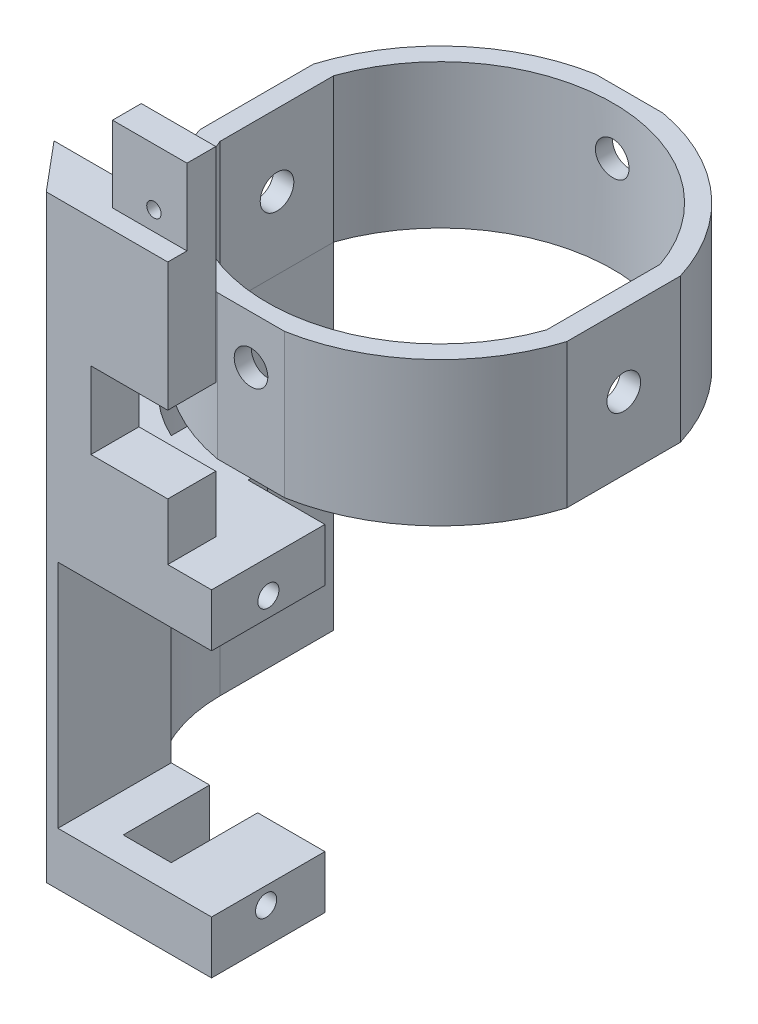
SolidWorks part; units mm, degrees
ref_plane "Front Plane" through (0, 0, 0) normal (0, 0, 1) x (1, 0, 0)
ref_plane "Top Plane" through (0, 0, 0) normal (0, 1, 0) x (1, 0, 0)
ref_plane "Right Plane" through (0, 0, 0) normal (1, 0, 0) x (0, 0, -1)
sketch "Sketch1" plane through (0, 0, 0) normal (0, 1, 0) x (1, 0, 0)
  line L0 (17, 5.9161) -> (17, -5.9161)
  line L1 (-17, -5.9161) -> (-17, 5.9161)
  line L2 (19.105, 5.9161) -> (19.105, -5.9161)
  line L3 (-19.105, 5.9161) -> (-19.105, -5.9161)
  line L4 (-19.105, -5.9161) -> (-19.105, -20)
  line L10 (-19.105, 5.9161) -> (-17, 5.9161)
  line L11 (0, -20) -> (0, -18)
  line L12 (-3.5, 19.6914) -> (3.5, 19.6914)
  line L13 (0, -20) -> (8.0017, -20)
  line L14 (8.0017, -20) -> (8.0017, -31.8)
  line L15 (8.0017, -31.8) -> (-9.2094, -31.8)
  line L16 (-9.2094, -31.8) -> (-19.105, -20)
  arc A0 (17, 5.9161) -> (-17, 5.9161) centre (0, 0) ccw
  arc A1 (-17, -5.9161) -> (17, -5.9161) centre (0, 0) ccw
  arc A2 (-19.105, -5.9161) -> (19.105, -5.9161) centre (0, 0) ccw
  arc A3 (19.105, 5.9161) -> (-19.105, 5.9161) centre (0, 0) ccw
  circle A4 centre (0, 0) radius 36.5
  point P1 (-19.105, 0)
  point P7 (-17, 0)
  point P8 (17, 0)
  point P13 (19.105, 0)
  dimension "D1" = 36
  dimension "D4" = 40
  dimension "D5" = 73
  dimension "D2" = 17
  dimension "D3" = 17
  dimension "D6" = 7
  dimension "D7" = 11.8
extrude "Boss-Extrude2" add sketch "Sketch1" along normal blind 15 contours L2 A3 L3 A2 A1 L1 A0 L0 | L3 A2 L11 A1 L1 L10 region at (0, 0, -18.5509) region at (-17.322, 0, 0)
extrude "Boss-Extrude3" add sketch "Sketch1<3>" against normal blind 35 separate body contours A2 L4 region at (-5.7221, 0, 23.485)
sketch "Sketch1<3>" plane through (0, 0, 0) normal (0, 1, 0) x (1, 0, 0) same geometry as "Sketch1"
extrude "Boss-Extrude4" add sketch "Sketch1<4>" against normal blind 35 contours L3 A2 L11 A1 L1 L10 region at (-17.322, 0, 0)
sketch "Sketch1<4>" plane through (0, 0, 0) normal (0, 1, 0) x (1, 0, 0) same geometry as "Sketch1"
sketch "Sketch2" plane through (8.0017, 0, 0) normal (1, 0, 0) x (0, 0, -1)
  line L0 (-31.8, -35) -> (-31.8, 0) construction
  line L1 (-31.8, -5.5) -> (-20, -5.5)
  line L2 (-31.8, -5.5) -> (-31.8, -29.5)
  line L3 (-31.8, -29.5) -> (-20, -29.5)
  line L4 (-20, -5.5) -> (-20, -29.5)
  line L5 (-20, -35) -> (-20, 0) construction
  line L6 (-20, 0) -> (-31.8, 0) construction
  dimension "D1" = 24
  dimension "D2" = 5.5
extrude "Cut-Extrude1" cut sketch "Sketch2" against normal blind 16
sketch "Sketch5" plane through (0, 0, 0) normal (1, 0, 0) x (0, 0, -1)
  line L1 (-20, -5.5) -> (-17.5652, -5.5)
  line L2 (-20, -5.5) -> (-20, -35.189)
  line L3 (-20, -35.189) -> (-17.5652, -35.189)
  line L4 (-17.5652, -5.5) -> (-17.5652, -35.189)
extrude "Cut-Extrude7" cut sketch "Sketch5" against normal blind 8
sketch "Sketch6" plane through (0, -35, 0) normal (0, -1, 0) x (-1, 0, 0)
  line L1 (8, -17.5652) -> (3.6822, -17.5652)
  line L2 (8, -17.5652) -> (8, -16.1081)
  line L3 (8, -16.1081) -> (3.6822, -16.1081)
  line L4 (3.6822, -17.5652) -> (3.6822, -16.1081)
extrude "Cut-Extrude8" cut sketch "Sketch6" against normal blind 29.5
sketch "Sketch7" plane through (0, 0, 0) normal (0, 1, 0) x (1, 0, 0)
  line L0 (-13.4024, -26.8) -> (-9.2094, -31.8)
  line L1 (-9.2094, -31.8) -> (-19.105, -20) construction
  line L2 (-9.2094, -31.8) -> (3.4392, -31.8)
  line L3 (8.0017, -31.8) -> (-9.2094, -31.8) construction
  line L4 (3.4392, -31.8) -> (3.4392, -26.8)
  line L5 (3.4392, -26.8) -> (-13.4024, -26.8)
  dimension "D1" = 5
extrude "Boss-Extrude6" add sketch "Sketch7" along normal blind 40
sketch "Sketch8" plane through (0, 0, 31.8) normal (0, 0, 1) x (1, 0, 0)
  line L0 (-9.2094, 40) -> (3.4392, 40) construction
  line L1 (-4.3135, 40) -> (3.4392, 40)
  line L2 (-4.3135, 40) -> (-4.3135, 27.2825)
  line L3 (-4.3135, 27.2825) -> (3.4392, 27.2825)
  line L4 (3.4392, 40) -> (3.4392, 27.2825)
  line L5 (3.4392, 40) -> (3.4392, 0) construction
extrude "Cut-Extrude9" cut sketch "Sketch8" against normal blind 2
sketch "Sketch9" plane through (0, 15, 0) normal (0, 1, 0) x (1, 0, 0)
  line L0 (-3.5, -19.6914) -> (3.5, -19.6914)
  arc A0 (-19.105, -5.9161) -> (19.105, -5.9161) centre (0, 0) ccw construction
  arc A1 (-3.5, -19.6914) -> (3.5, -19.6914) centre (0, 0) ccw
  point P5 (0, -19.6914)
  dimension "D1" = 7
extrude "Cut-Extrude10" cut sketch "Sketch9" against normal blind 15
sketch "Sketch10" plane through (0, -29.5, 0) normal (0, 1, 0) x (1, 0, 0)
  line L0 (-7.9983, -20) -> (8.0017, -20) construction
  line L1 (-3.9983, -20) -> (1.0017, -20)
  line L2 (-3.9983, -20) -> (-3.9983, -29)
  line L3 (-3.9983, -29) -> (1.0017, -29)
  line L4 (1.0017, -20) -> (1.0017, -29)
  line L5 (-7.9983, -31.8) -> (-7.9983, -20) construction
  dimension "D1" = 9
  dimension "D2" = 5
  dimension "D3" = 4
extrude "Cut-Extrude11" cut sketch "Sketch10" against normal blind 10
sketch "Sketch11" plane through (0, 0, 31.8) normal (0, 0, 1) x (1, 0, 0)
  line L1 (-4.3135, 27.2825) -> (-13.4024, 27.2825)
  line L2 (-4.3135, 27.2825) -> (-4.3135, 40)
  line L3 (-4.3135, 40) -> (-13.4024, 40)
  line L4 (-13.4024, 27.2825) -> (-13.4024, 40)
extrude "Cut-Extrude12" cut sketch "Sketch11" against normal blind 5
sketch "Sketch12" plane through (-19.105, 0, 0) normal (-1, 0, 0) x (0, 0, 1)
  line L0 (-5.9161, 15) -> (5.9161, 15) construction
  line L1 (-5.9161, 15) -> (-5.9161, 0) construction
  circle A0 centre (-0.0161, 7.5) radius 1.75
  dimension "D3" = 3.5
  dimension "D1" = 7.5
  dimension "D2" = 5.9
extrude "Cut-Extrude13" cut sketch "Sketch12" against normal blind 40
sketch "Sketch14" plane through (0, -35, 0) normal (0, -1, 0) x (1, 0, 0)
  line L0 (-8, 20) -> (-8, 16.1245)
  arc A0 (-17, 5.9161) -> (-8, 20) centre (-1.4802, 5.9161) cw
  arc A1 (-8, 16.1245) -> (-17, 5.9161) centre (0, 0) ccw
extrude "Cut-Extrude14" cut sketch "Sketch14" against normal blind 35
sketch "Sketch15" plane through (0, 0, -19.6914) normal (0, 0, -1) x (-1, 0, 0)
  line L0 (3.5, 15) -> (-3.5, 15) construction
  line L1 (3.5, 15) -> (3.5, 0) construction
  circle A0 centre (0, 10) radius 1.75
  dimension "D1" = 3.5
  dimension "D2" = 5
  dimension "D3" = 3.5
extrude "Cut-Extrude15" cut sketch "Sketch15" against normal blind 60
sketch "Sketch17" plane through (8.0017, 0, 0) normal (1, 0, 0) x (0, 0, -1)
  circle A0 centre (-25.8814, -3.4837) radius 1.1
extrude "Cut-Extrude17" cut sketch "Sketch17" against normal blind 6
sketch "Sketch18" plane through (8.0017, 0, 0) normal (1, 0, 0) x (0, 0, -1)
  circle A0 centre (-26.1207, -31.2826) radius 1.1
extrude "Cut-Extrude18" cut sketch "Sketch18" against normal blind 6
sketch "Sketch19" plane through (0, 0, 29.8) normal (0, 0, 1) x (1, 0, 0)
  line L0 (-4.3135, 27.2825) -> (3.4392, 27.2825) construction
  circle A0 centre (0, 29.2825) radius 0.75
  dimension "D1" = 1.5
  dimension "D2" = 2
sketch "Sketch20" plane through (0, 0, 29.8) normal (0, 0, 1) x (1, 0, 0)
  line L0 (3.4392, 27.2825) -> (3.4392, 40) construction
  line L1 (-4.3135, 40) -> (3.4392, 40)
  line L2 (-4.3135, 40) -> (-4.3135, 35.1962)
  line L3 (-4.3135, 35.1962) -> (3.4392, 35.1962)
  line L4 (3.4392, 40) -> (3.4392, 35.1962)
extrude "Cut-Extrude19" cut sketch "Sketch20" against normal blind 5
extrude "Cut-Extrude20" cut sketch "Sketch19" against normal blind 5 contours A0
sketch "Sketch21" plane through (0, 0, 31.8) normal (0, 0, 1) x (1, 0, 0)
  line L0 (3.4392, 27.2825) -> (3.4392, 0) construction
  line L1 (3.4392, 13.9182) -> (-4.5608, 13.9182)
  line L2 (3.4392, 13.9182) -> (3.4392, 5.9182)
  line L3 (3.4392, 5.9182) -> (-4.5608, 5.9182)
  line L4 (-4.5608, 13.9182) -> (-4.5608, 5.9182)
  dimension "D1" = 8
  dimension "D2" = 8
extrude "Cut-Extrude21" cut sketch "Sketch21" against normal blind 10
